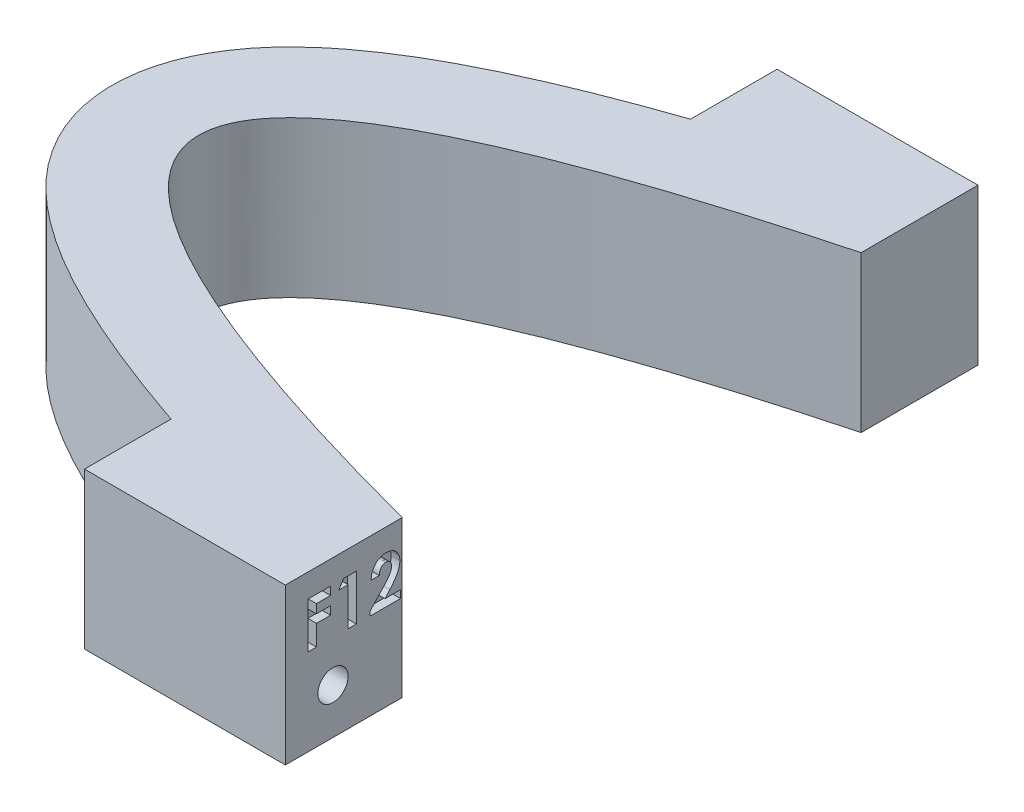
SolidWorks part; units mm, degrees
ref_plane "Front Plane" through (0, 0, 0) normal (0, 0, 1) x (1, 0, 0)
ref_plane "Top Plane" through (0, 0, 0) normal (0, 1, 0) x (1, 0, 0)
ref_plane "Right Plane" through (0, 0, 0) normal (1, 0, 0) x (0, 0, -1)
sketch "Sketch1" plane through (0, 0, 0) normal (0, 1, 0) x (1, 0, 0)
  line L0 (-77.2025, 32.0286) -> (-77.2025, -47.9714)
  line L1 (-77.2025, -47.9714) -> (-0.0375, -47.9714)
  line L2 (-0.0375, -47.9714) -> (-0.0375, -34.4714)
  line L3 (-77.2025, 32.0286) -> (-0.0358, 32.0286)
  line L4 (-0.0358, 32.0286) -> (-0.0358, 18.5286)
  line L5 (-50.0358, 32.0286) -> (-50.0358, -47.9714) construction
  line L6 (-23.2392, 22.0286) -> (-23.2392, 22.0286)
  line L7 (-67.2025, 22.0286) -> (-23.2392, 22.0286)
  line L8 (-67.2025, 22.0286) -> (-67.2025, -37.9714)
  line L9 (-67.2025, -37.9714) -> (-23.2397, -37.9714)
  line L10 (-23.2397, -37.9714) -> (-23.2397, -37.9714)
  line L11 (-23.2392, 22.0286) -> (-23.2392, 32.0286)
  line L12 (-23.2397, -37.9714) -> (-23.2397, -47.9714)
  spline S0 degree 2 poles (-0.0375, -34.4714) (-100.035, -7.9707) (-0.0358, 18.5286) knots 0 0 0 1 1 1
  spline S1 degree 1 poles (-23.2397, -37.9714) (-23.2392, 22.0286) knots 0 0 1 1 construction
  spline S2 degree 2 poles (-23.2397, -37.9714) (-29.1371, -35.9577) (-39.0408, -31.7935) (-47.1665, -27.3807) (-52.6334, -23.1384) (-56.3436, -19.1352) (-58.8048, -14.7402) (-59.8215, -11.0741) (-60.1073, -7.9712) (-59.8214, -4.8682) (-58.8047, -1.2022) (-56.3434, 3.1928) (-52.6332, 7.196) (-47.1662, 11.4382) (-39.0405, 15.8508) (-29.1367, 20.015) (-23.2392, 22.0286) knots 0.11249 0.11249 0.11249 0.185148 0.257805 0.330463 0.378901 0.427339 0.463668 0.487887 0.512107 0.536326 0.572655 0.621093 0.669531 0.742189 0.814846 0.887504 0.887504 0.887504
  dimension "D2" = 50
  dimension "D1" = 80
  dimension "D3" = 10
  dimension "D4" = 53
  dimension "D5" = 13.5
  dimension "D6" = 13.5
extrude "Boss-Extrude1" add sketch "Sketch1" along normal blind 18 contours S2 L12 L1 L2 S0 L4 L3 L11 region at (-11.6375, 0, -31.0286)
sketch "Sketch2" plane through (-0.0375, 0, 0) normal (1, 0, 0) x (0, 0, -1)
  line L0 (-47.9714, 18) -> (-34.4714, 18) construction
  line L3 (32.0286, 18) -> (18.5286, 18) construction
  circle A0 centre (-42.4714, 5.25) radius 1.75
  circle A1 centre (27.5286, 5.25) radius 1.75
  dimension "D3" = 3.5
  dimension "D4" = 3.5
  dimension "D1" = 12.75
  dimension "D2" = 12.75
extrude "Cut-Extrude1" cut sketch "Sketch2" against normal through all
sketch "Sketch3" plane through (-0.0375, 0, 0) normal (1, 0, 0) x (0, 0, -1)
  text T0 "<b>F12</b>" font "Century Gothic" height in points 20
extrude "Cut-Extrude2" cut sketch "Sketch3" against normal blind 1
sketch "Sketch4" plane through (-77.2025, 0, 0) normal (-1, 0, 0) x (0, 0, 1)
  line L1 (-25.3918, 2.9011) -> (-24.4259, 5.926)
  line L2 (-24.4259, 5.926) -> (-26.5627, 8.275)
  line L3 (-26.5627, 8.275) -> (-29.6653, 7.5989)
  line L4 (-29.6653, 7.5989) -> (-30.6312, 4.574)
  line L5 (-30.6312, 4.574) -> (-28.4944, 2.225)
  line L6 (-28.4944, 2.225) -> (-25.3918, 2.9011)
  line L7 (44.7168, 3.0046) -> (45.5387, 6.0719)
  line L8 (45.5387, 6.0719) -> (43.2933, 8.3172)
  line L9 (43.2933, 8.3172) -> (40.2261, 7.4954)
  line L10 (40.2261, 7.4954) -> (39.4042, 4.4281)
  line L11 (39.4042, 4.4281) -> (41.6496, 2.1828)
  line L12 (41.6496, 2.1828) -> (44.7168, 3.0046)
  circle A0 centre (-27.5286, 5.25) radius 2.75 construction
  circle A1 centre (42.4714, 5.25) radius 2.75 construction
  dimension "D1" = 5.5
extrude "Cut-Extrude3" cut sketch "Sketch4" against normal blind 5 from surface starting at face at (-23.2397, 5.25, 40.7214)
